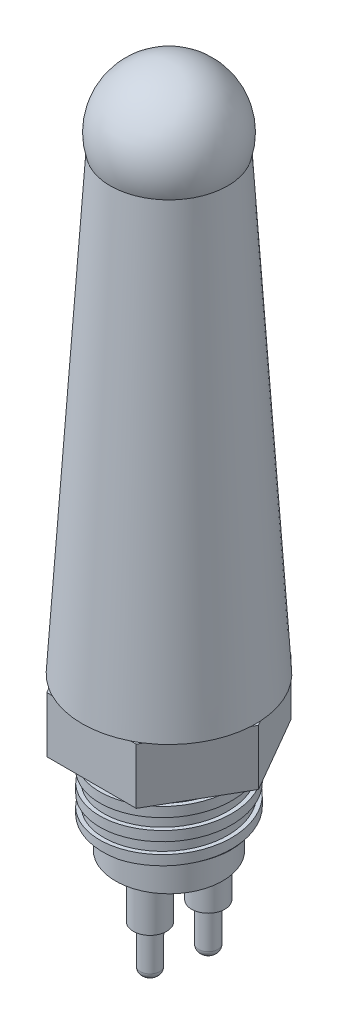
SolidWorks part; units mm, degrees
ref_plane "Front Plane" through (0, 0, 0) normal (0, 0, 1) x (1, 0, 0)
ref_plane "Top Plane" through (0, 0, 0) normal (0, 1, 0) x (1, 0, 0)
ref_plane "Right Plane" through (0, 0, 0) normal (1, 0, 0) x (0, 0, -1)
sketch "Sketch1" plane through (0, 0, 0) normal (0, 0, 1) x (1, 0, 0)
  line L0 (0, 0) -> (0, 79.7501) construction
  line L1 (-8.4535, 68.5049) -> (-12.5, 3.5049)
  line L2 (-12.5, 3.5049) -> (0, 3.5049)
  line L3 (0, 79.7501) -> (0, 3.5049)
  arc A0 (0, 79.7501) -> (-8.4535, 68.5049) centre (0, 70.9501) ccw
  dimension "D1" = 65
  dimension "D3" = 8.8
  dimension "D2" = 12.5
revolve "Revolve1" add sketch "Sketch1" angle 360 about L0
sketch "Sketch2" plane through (0, 3.5049, 0) normal (0, -1, 0) x (1, 0, 0)
  line L1 (12.8749, 0) -> (6.4375, 11.15)
  line L2 (6.4375, 11.15) -> (-6.4375, 11.15)
  line L3 (-6.4375, 11.15) -> (-12.8749, 0)
  line L4 (-12.8749, 0) -> (-6.4375, -11.15)
  line L5 (-6.4375, -11.15) -> (6.4375, -11.15)
  line L6 (6.4375, -11.15) -> (12.8749, 0)
  circle A0 centre (0, 0) radius 11.15 construction
extrude "Boss-Extrude1" add sketch "Sketch2" along normal blind 8
sketch "Sketch3" plane through (0, -4.4951, 0) normal (0, -1, 0) x (1, 0, 0)
  circle A0 centre (0, 0) radius 9.5
extrude "Boss-Extrude2" add sketch "Sketch3" along normal blind 9.5
sketch3d "3DSketch1"
  line L1 (-9.5, -13.4418, 0) -> (-8.9227, -13.4418, 0)
  line L2 (-9.5, -13.4418, 0) -> (-9.5, -11.8418, 0)
  line L3 (-9.5, -11.8418, 0) -> (-8.9227, -11.8418, 0)
  line L4 (-8.9227, -13.4418, 0) -> (-8.9227, -11.8418, 0)
  dimension "D1" = 1.6
sketch "Sketch7" plane through (0, -13.9951, 0) normal (0, -1, 0) x (1, 0, 0)
  circle A0 centre (0, 0) radius 9.5
curve "Helix/Spiral1" pitch 3 height 12 turns 4
sweep "Cut-Sweep1" cut profiles "3DSketch1" path "Helix/Spiral1" align with end faces yes
sketch "Sketch14" plane through (0, -13.9951, 0) normal (0, -1, 0) x (1, 0, 0)
  circle A0 centre (0, 0) radius 7.7
extrude "Boss-Extrude3" add sketch "Sketch14" along normal blind 4.5
sketch "Sketch15" plane through (0, -18.4951, 0) normal (0, -1, 0) x (1, 0, 0)
  circle A0 centre (1.5581, 4.2922) radius 2.4
  circle A1 centre (2.9893, -2.6578) radius 2.4
  circle A2 centre (-3.9447, -2.1862) radius 2.4
  circle A3 centre (0, 0) radius 7.7 construction
  dimension "D6" = 4.8
  dimension "D1" = 6.95
  dimension "D2" = 6.95
  dimension "D3" = 8.5
  dimension "D4" = 4
  dimension "D5" = 4.51
extrude "Boss-Extrude4" add sketch "Sketch15" along normal blind 6
sketch "Sketch16" plane through (0, -24.4951, 0) normal (0, -1, 0) x (1, 0, 0)
  circle A0 centre (-3.9447, -2.1862) radius 1.4
  circle A1 centre (-3.9447, -2.1862) radius 2.4 construction
  circle A2 centre (2.9893, -2.6578) radius 1.4
  circle A3 centre (2.9893, -2.6578) radius 2.4 construction
  circle A4 centre (1.5581, 4.2922) radius 1.4
  circle A5 centre (1.5581, 4.2922) radius 2.4 construction
  dimension "D1" = 2.8
extrude "Boss-Extrude5" add sketch "Sketch16" along normal blind 6.5
fillet "Fillet1" radius 1 3 edges at (2.9893, -30.9951, -4.0578) (1.5581, -30.9951, 2.8922) (-3.9447, -30.9951, -3.5862)
other "Parting Line2" [suppressed]
other "Parting Surface1" [suppressed] parameters "D1"=10
sketch "Sketch17" [suppressed] plane through (0, 0, 0) normal (1, 0, 0) x (0, 0, -1)
  line L1 (24.2073, -5.3557) -> (-22.8755, -5.3557)
  line L2 (24.2073, -5.3557) -> (24.2073, 89.2486)
  line L3 (24.2073, 89.2486) -> (-22.8755, 89.2486)
  line L4 (-22.8755, -5.3557) -> (-22.8755, 89.2486)
